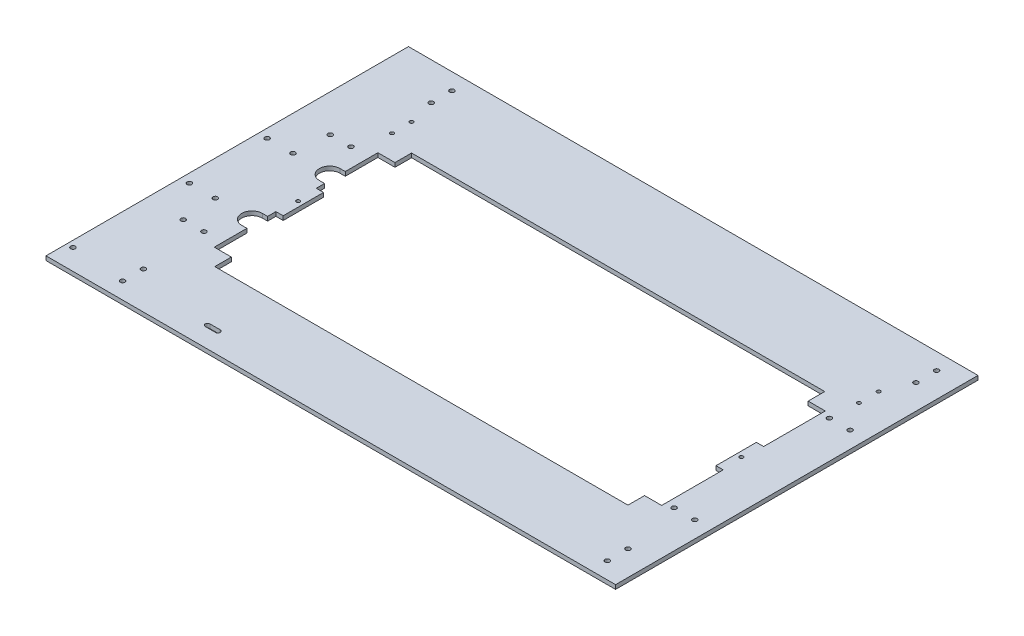
SolidWorks part; units mm, degrees
material "1060 Alloy"
ref_plane "Front Plane" through (0, 0, 0) normal (0, 0, 1) x (1, 0, 0)
ref_plane "Top Plane" through (0, 0, 0) normal (0, 1, 0) x (1, 0, 0)
ref_plane "Right Plane" through (0, 0, 0) normal (1, 0, 0) x (0, 0, -1)
sketch "Sketch1" plane through (0, 0, 0) normal (0, 1, 0) x (1, 0, 0)
  line L0 (-216, 79) -> (216, -79) construction
  line L1 (-290, -167.5) -> (260, -167.5)
  line L2 (-290, -167.5) -> (-290, 182.5)
  line L3 (-290, 182.5) -> (260, 182.5)
  line L4 (260, -167.5) -> (260, 182.5)
  line L5 (-216, -79) -> (216, -79)
  line L6 (-216, -79) -> (-216, 79)
  line L7 (-216, 79) -> (216, 79)
  line L8 (216, -79) -> (216, 79)
  dimension "D1" = 432
  dimension "D2" = 158
  dimension "D3" = 88.5
  dimension "D4" = 74
  dimension "D5" = 550
  dimension "D6" = 350
sheet metal parameters "Sheet-Metal1" thickness 4 parameters "D1"=5
base flange "Base-Flange1" sketch "Sketch1" thickness 4 reverse thickness direction no parameters "D1"=5
sketch "Sketch4" plane through (0, 0, 0) normal (0, 1, 0) x (1, 0, 0)
  line L0 (199.5, 0) -> (216, 0) construction
  line L1 (-199.5, 95) -> (199.5, 95)
  line L2 (-199.5, 95) -> (-199.5, -95)
  line L3 (-199.5, -95) -> (199.5, -95)
  line L4 (199.5, 95) -> (199.5, -95)
  line L5 (216, -79) -> (216, 79) construction
  line L6 (-199.5, 95) -> (199.5, -95) construction
  line L7 (216, 79) -> (-216, 79) construction
  line L8 (-216, 79) -> (-216, -79) construction
  dimension "D1" = 16
  dimension "D2" = 16.5
extrude "Cut-Extrude1" cut sketch "Sketch4" against normal through all normal cut yes
sketch "Sketch5" plane through (0, -4, 0) normal (0, -1, 0) x (1, 0, 0)
  line L0 (-234, 71) -> (-254, 71) construction
  line L1 (-244, 71) -> (-71.0163, 71) construction
  line L2 (-216, -79) -> (-216, 79) construction
  line L3 (224, 75) -> (244, 75) construction
  line L4 (-199.5, 95) -> (199.5, 95) construction
  line L5 (0, 95) -> (0, 116.857) construction
  line L6 (244, 75) -> (71.0163, 75) construction
  line L7 (234, 71) -> (254, 71) construction
  line L8 (-216, 79) -> (-199.5, 79) construction
  line L9 (216, 79) -> (216, -79) construction
  line L10 (0, 0) -> (-177.0468, 0) construction
  line L11 (234, -71) -> (254, -71) construction
  line L12 (244, -75) -> (71.0163, -75) construction
  line L13 (-234, -71) -> (-254, -71) construction
  line L14 (216, 0) -> (248.6013, 0) construction
  line L15 (199.5, 79) -> (216, 79) construction
  circle A0 centre (-254, 71) radius 2.25
  circle A1 centre (-234, 71) radius 2.25
  circle A2 centre (234, 71) radius 2.25 construction
  circle A3 centre (254, 71) radius 2.25 construction
  circle A4 centre (254, -71) radius 2.25 construction
  circle A5 centre (234, -71) radius 2.25 construction
  circle A6 centre (-234, -71) radius 2.25
  circle A7 centre (-254, -71) radius 2.25
  circle A8 centre (224, 75) radius 2.25
  circle A9 centre (244, 75) radius 2.25
  circle A10 centre (224, -75) radius 2.25
  circle A11 centre (244, -75) radius 2.25
  dimension "D2" = 4.5
  dimension "D4" = 18
  dimension "D5" = 8
  dimension "D1" = 20
  dimension "D3" = 8
  dimension "D6" = 4
extrude "Cut-Extrude2" cut sketch "Sketch5" against normal through all normal cut yes
sketch "Sketch6" plane through (0, 0, 0) normal (0, 1, 0) x (1, 0, 0)
  line L0 (-225.5, 121) -> (-225.5, 102) construction
  line L1 (0, 95) -> (0, 143.2453) construction
  line L2 (199.5, 95) -> (-199.5, 95) construction
  line L4 (-225.5, 111.5) -> (-199.5, 111.5) construction
  line L5 (-199.5, 111.5) -> (-199.5, 95) construction
  circle A0 centre (-225.5, 102) radius 1.75
  circle A1 centre (-225.5, 121) radius 1.75
  circle A2 centre (225.5, 102) radius 1.75
  circle A3 centre (225.5, 121) radius 1.75
  dimension "D2" = 3.5
  dimension "D1" = 19
  dimension "D3" = 16.5
  dimension "D4" = 26
extrude "Cut-Extrude3" cut sketch "Sketch6" against normal through all normal cut yes
sketch "Sketch7" plane through (0, 0, 0) normal (0, 1, 0) x (1, 0, 0)
  line L0 (199.5, 95) -> (-199.5, 95) construction
  line L1 (-199.5, 95) -> (-199.5, 79) construction
  line L2 (0, 0) -> (-290, 0) construction
  line L3 (-290, 182.5) -> (-290, -167.5) construction
  line L4 (0, 95) -> (0, 61.1102) construction
  circle A0 centre (-254.5, 115) radius 4.5
  circle A1 centre (-254.5, -115) radius 4.5
  circle A2 centre (254.5, -115) radius 4.5
  circle A3 centre (254.5, 115) radius 4.5
  dimension "D1" = 9
  dimension "D2" = 20
  dimension "D3" = 55
extrude "Cut-Extrude4" [suppressed] cut sketch "Sketch7" against normal through all
sketch "Sketch8" plane through (0, 0, 0) normal (0, 1, 0) x (1, 0, 0)
  line L0 (-232, 166.5) -> (-232, 146.5) construction
  line L1 (-290, 182.5) -> (-290, -167.5) construction
  line L2 (-232, -131.5) -> (-232, -151.5) construction
  line L3 (260, 182.5) -> (-290, 182.5) construction
  line L4 (-290, -167.5) -> (260, -167.5) construction
  line L5 (236, 166.5) -> (236, 146.5) construction
  line L6 (236, -131.5) -> (236, -151.5) construction
  line L7 (260, -167.5) -> (260, 182.5) construction
  circle A0 centre (-232, 146.5) radius 2.25
  circle A1 centre (-232, 166.5) radius 2.25
  circle A2 centre (-232, -151.5) radius 2.25
  circle A3 centre (-232, -131.5) radius 2.25
  circle A4 centre (236, 146.5) radius 2.25
  circle A5 centre (236, 166.5) radius 2.25
  circle A6 centre (236, -151.5) radius 2.25
  circle A7 centre (236, -131.5) radius 2.25
  dimension "D1" = 4.5
  dimension "D9" = 16
  dimension "D2" = 20
  dimension "D3" = 58
  dimension "D5" = 16
  dimension "D6" = 16
  dimension "D8" = 24
  dimension "D4" = 2
  dimension "D7" = 2
extrude "Cut-Extrude5" cut sketch "Sketch8" against normal through all normal cut yes
sketch "Sketch10" plane through (0, 0, 0) normal (0, 1, 0) x (1, 0, 0)
  line L0 (-149, -147.5) -> (-284, -147.5) construction
  line L1 (-284, -147.5) -> (-290, -147.5) construction
  line L2 (-290, 182.5) -> (-290, -167.5) construction
  line L3 (-290, -167.5) -> (260, -167.5) construction
  line L4 (-154, -147.5) -> (-144, -147.5) construction
  line L5 (-154, -145.25) -> (-144, -145.25)
  line L6 (-154, -149.75) -> (-144, -149.75)
  circle A0 centre (-284, -147.5) radius 2.25
  circle A1 centre (-149, -147.5) radius 2.25 construction
  arc A2 (-154, -145.25) -> (-154, -149.75) centre (-154, -147.5) ccw
  arc A3 (-144, -149.75) -> (-144, -145.25) centre (-144, -147.5) ccw
  point P11 (-149, -147.5)
  dimension "D2" = 4.5
  dimension "D1" = 6
  dimension "D3" = 135
  dimension "D4" = 20
  dimension "D5" = 10
extrude "Cut-Extrude7" cut sketch "Sketch10" against normal through all normal cut yes
sketch "Sketch11" plane through (0, 0, 0) normal (0, 1, 0) x (1, 0, 0)
  line L0 (-216, -79) -> (-216, 79) construction
  line L1 (-216, 19.5) -> (-209, 19.5)
  line L2 (-216, 19.5) -> (-216, -19.5)
  line L3 (-216, -19.5) -> (-209, -19.5)
  line L4 (-209, 19.5) -> (-209, -19.5)
  line L5 (-216, -19.5) -> (-216, -79) construction
  line L6 (-216, 19.5) -> (-216, 79) construction
  line L7 (-216, 79) -> (-216, 66.3542) construction
  line L8 (0, 95) -> (0, 0) construction
  line L9 (199.5, 95) -> (-199.5, 95) construction
  line L10 (216, 79) -> (216, 66.3542) construction
  line L11 (216, 19.5) -> (216, 79) construction
  line L12 (216, -19.5) -> (216, -79) construction
  line L13 (209, 19.5) -> (209, -19.5)
  line L14 (216, -19.5) -> (209, -19.5)
  line L15 (216, 19.5) -> (216, -19.5)
  line L16 (216, 19.5) -> (209, 19.5)
  dimension "D1" = 39
  dimension "D2" = 7
base flange "Tab1" sketch "Sketch11" thickness 4 reverse thickness direction no parameters "D1"=5
sketch "Sketch12" plane through (0, 0, 0) normal (0, 1, 0) x (1, 0, 0)
  line L0 (214, 0) -> (0, 0) construction
  line L1 (0, 0) -> (-214, 0) construction
  line L2 (-216, 79) -> (-216, 19.5) construction
  circle A0 centre (-214, 0) radius 1.75
  circle A1 centre (214, 0) radius 1.75
  dimension "D2" = 3.5
  dimension "D1" = 2
extrude "Cut-Extrude8" cut sketch "Sketch12" against normal through all normal cut yes
sketch "Sketch13" plane through (0, 0, 0) normal (0, 1, 0) x (1, 0, 0)
  line L0 (-221, -37.5) -> (169.7569, -37.5) construction
  line L1 (-221, -27.5) -> (169.7569, -27.5)
  line L2 (-221, -47.5) -> (169.7569, -47.5)
  line L3 (0, 0) -> (-113.688, 0) construction
  line L4 (-221, 37.5) -> (169.7569, 37.5) construction
  line L5 (-221, 27.5) -> (169.7569, 27.5)
  line L6 (-221, 47.5) -> (169.7569, 47.5)
  line L7 (-216, 79) -> (-216, 19.5) construction
  line L8 (0, 0) -> (0, 35) construction
  arc A0 (-221, -27.5) -> (-221, -47.5) centre (-221, -37.5) ccw
  arc A1 (169.7569, -47.5) -> (169.7569, -27.5) centre (169.7569, -37.5) ccw
  arc A2 (-221, 27.5) -> (-221, 47.5) centre (-221, 37.5) cw
  arc A3 (169.7569, 47.5) -> (169.7569, 27.5) centre (169.7569, 37.5) cw
  point P2 (-25.6215, -37.5)
  point P12 (-25.6215, 37.5)
  dimension "D1" = 5
  dimension "D2" = 20
  dimension "D3" = 75
extrude "Cut-Extrude9" cut sketch "Sketch13" against normal through all normal cut yes
sketch "Sketch14" plane through (0, 0, 0) normal (0, 1, 0) x (1, 0, 0)
  line L0 (-281.5, -37.5) -> (-256.5, -37.5) construction
  line L1 (-256.5, -37.5) -> (-256.5, 37.5) construction
  line L2 (-256.5, 37.5) -> (-281.5, 37.5) construction
  line L3 (-281.5, 37.5) -> (-281.5, -37.5) construction
  line L4 (-269, -37.5) -> (-269, -5.8303) construction
  line L5 (-290, 182.5) -> (-290, -167.5) construction
  line L6 (-256.5, 0) -> (-209, 0) construction
  line L7 (-209, -19.5) -> (-209, 19.5) construction
  circle A0 centre (-281.5, 37.5) radius 2.25
  circle A1 centre (-256.5, 37.5) radius 2.25
  circle A2 centre (-281.5, -37.5) radius 2.25
  circle A3 centre (-256.5, -37.5) radius 2.25
  dimension "D2" = 4.5
  dimension "D1" = 21
  dimension "D3" = 75
  dimension "D4" = 25
extrude "Cut-Extrude10" cut sketch "Sketch14" against normal through all normal cut yes
flat pattern "Flat-Pattern1" [suppressed]
sketch "Bend-Lines1" plane through (0, 0, 0) normal (0, 1, 0) x (1, 0, 0)
sketch3d "Bounding-Box1" [suppressed]
  line L0 (260, 182.5, 0) -> (-290, 182.5, 0) construction
  line L1 (260, -167.5, 0) -> (-290, -167.5, 0) construction
  line L2 (260, 182.5, 0) -> (260, -167.5, 0) construction
  line L3 (-290, 182.5, 0) -> (-290, -167.5, 0) construction
